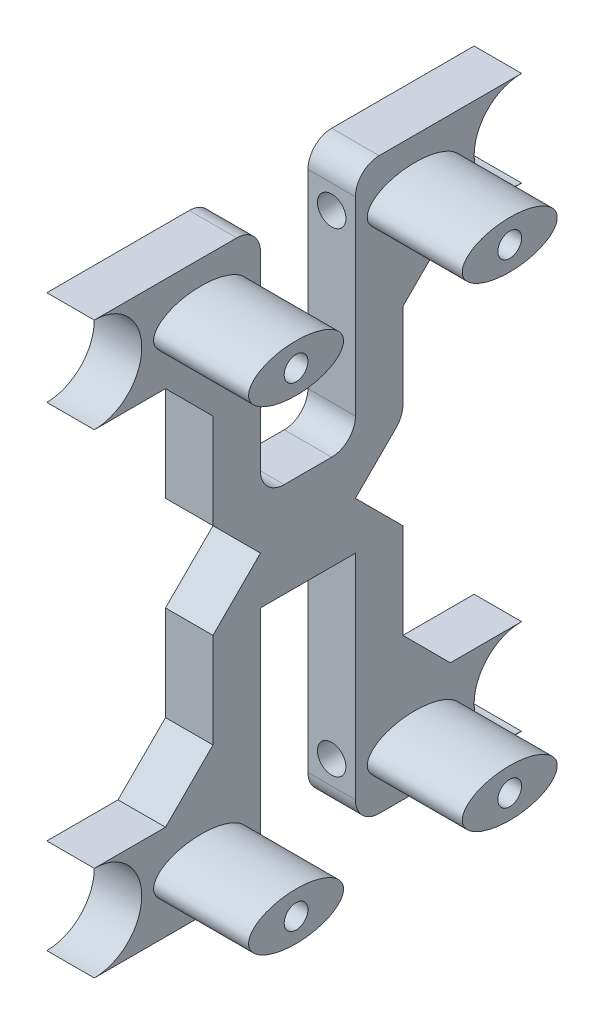
SolidWorks part; units mm, degrees
material "Copper"
ref_plane "Front Plane" through (0, 0, 0) normal (0, 0, 1) x (1, 0, 0)
ref_plane "Top Plane" through (0, 0, 0) normal (0, 1, 0) x (1, 0, 0)
ref_plane "Right Plane" through (0, 0, 0) normal (1, 0, 0) x (0, 0, -1)
sketch "Sketch1" plane through (0, 0, 0) normal (1, 0, 0) x (0, 0, -1)
  line L0 (0, 0) -> (0, 20)
  line L1 (0, 20) -> (20, 20)
  line L2 (20, 20) -> (20, 110)
  line L3 (30, 120) -> (90, 120)
  line L5 (90, 80) -> (60, 80)
  line L6 (60, 80) -> (40, 60)
  line L7 (40, 60) -> (40, 20)
  line L8 (40, 20) -> (20, 0)
  line L9 (20, 0) -> (0, 0)
  arc A1 (90, 120) -> (90, 80) centre (90, 100) ccw
  arc A2 (20, 110) -> (30, 120) centre (30, 110) cw
  circle A3 centre (45, 100) radius 5
  ellipse E0 centre (45, 100) end of major axis (25, 100) minor radius 10
  point P21 (20, 120)
  dimension "D3" = 40
  dimension "D7" = 10
  dimension "D12" = 10
  dimension "D1" = 20
  dimension "D2" = 20
  dimension "D4" = 70
  dimension "D5" = 40
  dimension "D6" = 45
  dimension "D8" = 25
  dimension "D9" = 20
  dimension "D10" = 10
  dimension "D11" = 20
extrude "Boss-Extrude1" add sketch "Sketch1" against normal blind 20 contours L2 A2 L3 A1 L5 L6 L7 L8 L9 L0 L1
extrude "Boss-Extrude2" add sketch "Sketch1<4>" along normal blind 40 contours A3 | E0
sketch "Sketch1<4>" plane through (0, 0, 0) normal (1, 0, 0) x (0, 0, -1) same geometry as "Sketch1"
sketch "Sketch2" plane through (0, 0, -20) normal (0, 0, 1) x (1, 0, 0)
  line L0 (-20, 120) -> (0, 120) construction
  line L1 (-20, 20) -> (-20, 110) construction
  circle A0 centre (-10, 100) radius 6
  dimension "D1" = 12
  dimension "D2" = 20
  dimension "D3" = 10
extrude "Cut-Extrude1" cut sketch "Sketch2" against normal blind 35
mirror "Mirror1" about plane through (-20, 0, 0) normal (0, 0, -1) of bodies 104
mirror "Mirror2" about plane through (-20, 0, -20) normal (0, 1, 0) of bodies 105
fillet "Fillet1" radius 10 3 edges at (-10, 20, -40) (-10, 20, -20) (-10, 20, 20)
